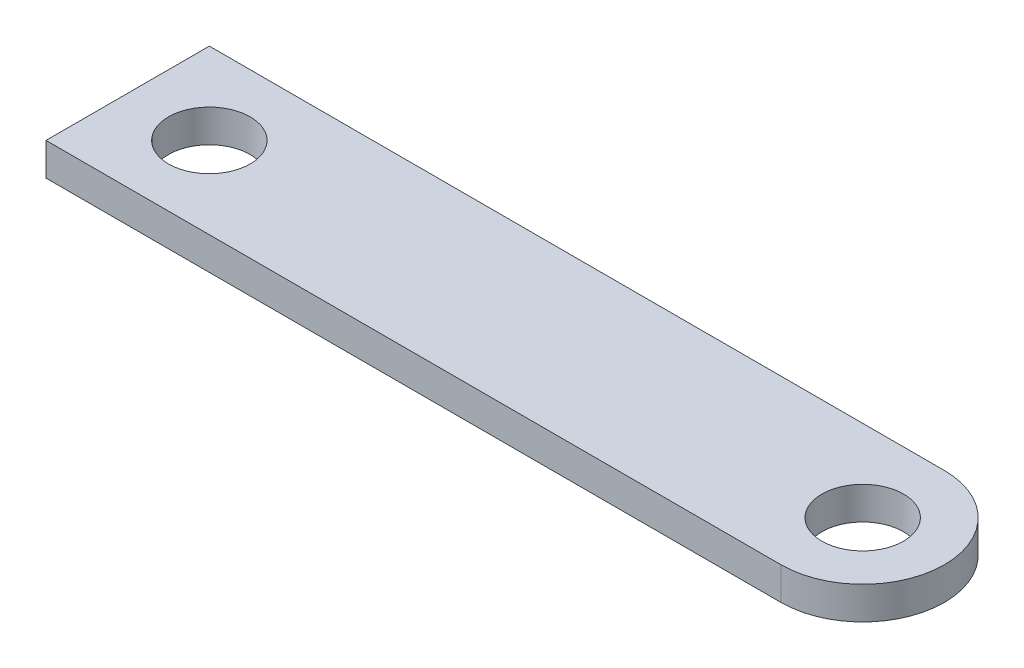
SolidWorks part; units mm, degrees
ref_plane "Alzado" through (0, 0, 0) normal (0, 0, 1) x (1, 0, 0)
ref_plane "Planta" through (0, 0, 0) normal (0, 1, 0) x (1, 0, 0)
ref_plane "Vista lateral" through (0, 0, 0) normal (1, 0, 0) x (0, 0, -1)
sketch "Croquis1" plane through (0, 0, 0) normal (0, 1, 0) x (1, 0, 0)
  line L0 (-22.5, 0) -> (27.5, 0)
  line L1 (-22.5, -5) -> (22.5, -5)
  line L2 (-22.5, -5) -> (-22.5, 5)
  line L3 (-22.5, 5) -> (22.5, 5)
  line L4 (22.5, -5) -> (22.5, 5)
  line L5 (-22.5, -5) -> (22.5, 5) construction
  line L6 (-22.5, 5) -> (22.5, -5) construction
  circle A0 centre (22.5, 0) radius 5
  circle A1 centre (22.5, 0) radius 2.5
  circle A2 centre (-17.5, 0) radius 2.5
  point P0 (0, 0)
  dimension "D3" = 5
  dimension "D4" = 5
  dimension "D1" = 45
  dimension "D2" = 10
extrude "Saliente-Extruir2" add sketch "Croquis1" along normal blind 2 contours A0 L3 L2 L1 | A1 L4 A0 | A1 L4 A0 region at (24.9757, 0, -2.4757) region at (20.0243, 0, -2.4757) region at (-1.1676, 0, 2.6102)
extrude "Saliente-Extruir5" add sketch "Croquis1<4>" along normal blind 2 contours A2 L0 A0 L3 L2 | A1 L0 A0 L4 | A1 L4 A0 L0 region at (24.9757, 0, 2.4757) region at (20.0243, 0, 2.4757) region at (-1.1676, 0, -2.6102)
sketch "Croquis1<4>" plane through (0, 0, 0) normal (0, 1, 0) x (1, 0, 0) same geometry as "Croquis1"
